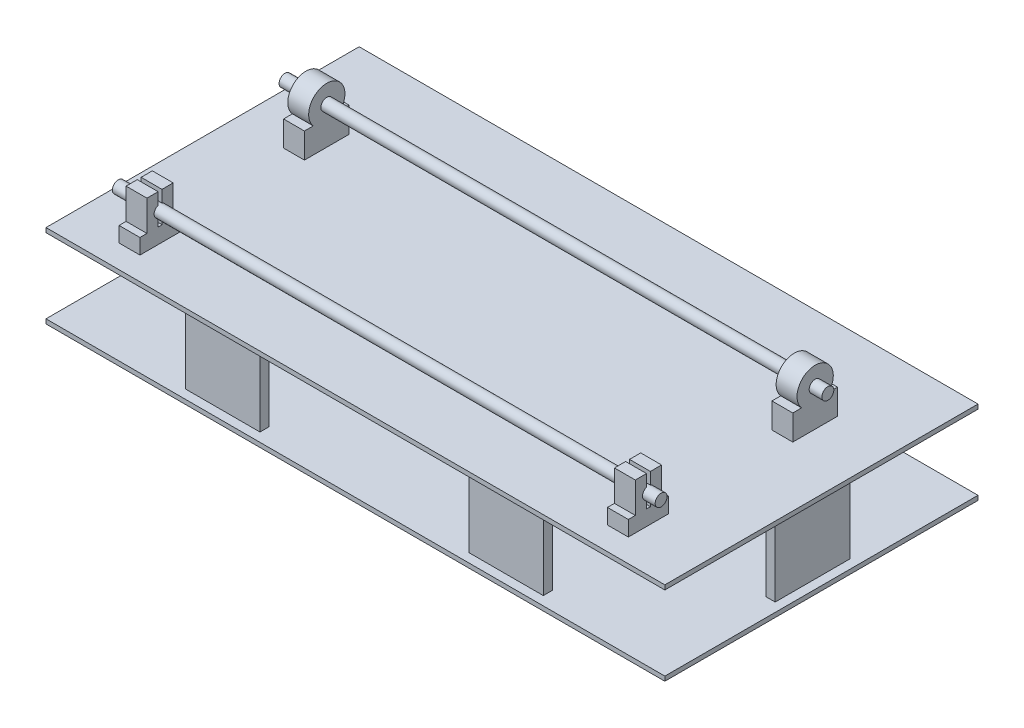
SolidWorks part; units mm, degrees
ref_plane "Front Plane" through (0, 0, 0) normal (0, 0, 1) x (1, 0, 0)
ref_plane "Top Plane" through (0, 0, 0) normal (0, 1, 0) x (1, 0, 0)
ref_plane "Right Plane" through (0, 0, 0) normal (1, 0, 0) x (0, 0, -1)
sketch "Sketch2" plane through (0, 0, 0) normal (0, 1, 0) x (1, 0, 0)
  line L1 (0, 0) -> (415, 0)
  line L2 (0, 0) -> (0, 210)
  line L3 (0, 210) -> (415, 210)
  line L4 (415, 0) -> (415, 210)
  dimension "D1" = 415
  dimension "D2" = 210
extrude "Boss-Extrude1" add sketch "Sketch2" along normal blind 3
ref_plane "Plane1" through (0, 53, 0) normal (0, 1, 0) x (1, 0, 0)
sketch "Sketch3" plane through (0, 53, 0) normal (0, 1, 0) x (1, 0, 0)
  line L8 (0, 210) -> (0, 0)
  line L9 (0, 0) -> (415, 0)
  line L10 (415, 0) -> (415, 210)
  line L11 (415, 210) -> (0, 210)
  line L12 (0, 210) -> (0, 0)
  line L13 (0, 0) -> (415, 0)
  line L14 (415, 0) -> (415, 210)
  line L15 (415, 210) -> (0, 210)
  dimension "D1" = 0
extrude "Boss-Extrude2" add sketch "Sketch3" along normal blind 3 separate body
sketch "Sketch4" plane through (0, 3, 0) normal (0, 1, 0) x (1, 0, 0)
  line L0 (0, 210) -> (0, 0) construction
  line L1 (6, 130) -> (12, 130)
  line L2 (6, 130) -> (6, 80)
  line L3 (6, 80) -> (12, 80)
  line L4 (12, 130) -> (12, 80)
  line L5 (87.5, 12) -> (137.5, 12)
  line L6 (87.5, 12) -> (87.5, 6)
  line L7 (87.5, 6) -> (137.5, 6)
  line L8 (137.5, 12) -> (137.5, 6)
  line L9 (277.5, 12) -> (327.5, 12)
  line L10 (277.5, 12) -> (277.5, 6)
  line L11 (277.5, 6) -> (327.5, 6)
  line L12 (327.5, 12) -> (327.5, 6)
  line L13 (409, 80) -> (403, 80)
  line L14 (409, 80) -> (409, 130)
  line L15 (409, 130) -> (403, 130)
  line L16 (403, 80) -> (403, 130)
  line L17 (327.5, 198) -> (277.5, 198)
  line L18 (327.5, 198) -> (327.5, 204)
  line L19 (327.5, 204) -> (277.5, 204)
  line L20 (277.5, 198) -> (277.5, 204)
  line L21 (137.5, 198) -> (87.5, 198)
  line L22 (137.5, 198) -> (137.5, 204)
  line L23 (137.5, 204) -> (87.5, 204)
  line L24 (87.5, 198) -> (87.5, 204)
  line L25 (0, 0) -> (415, 0) construction
  line L26 (415, 0) -> (415, 210) construction
  line L27 (415, 210) -> (0, 210) construction
  line L28 (0, 105) -> (415, 105) construction
  line L29 (207.5, 210) -> (207.5, 0) construction
  dimension "D1" = 50
  dimension "D2" = 6
  dimension "D3" = 50
  dimension "D4" = 6
  dimension "D5" = 50
  dimension "D6" = 6
  dimension "D7" = 50
  dimension "D8" = 6
  dimension "D9" = 50
  dimension "D10" = 6
  dimension "D11" = 50
  dimension "D12" = 6
  dimension "D13" = 6
  dimension "D14" = 6
  dimension "D15" = 6
  dimension "D16" = 6
  dimension "D17" = 6
  dimension "D18" = 6
  dimension "D19" = 70
  dimension "D20" = 70
  dimension "D21" = 70
  dimension "D22" = 70
  dimension "D23" = 25
  dimension "D24" = 25
extrude "Boss-Extrude3" add sketch "Sketch4" along normal up to surface (50 mm away) up to plane "Plane1"
ref_plane "Plane2" through (33.5, 0, 0) normal (-1, 0, 0) x (0, 0, 1)
sketch "Sketch5" plane through (33.5, 0, 0) normal (-1, 0, 0) x (0, 0, 1)
  line L0 (0, 56) -> (-210, 56) construction
  line L1 (-140.8, 81) -> (-140.8, 48.6428) construction
  line L2 (0, 56) -> (0, 53) construction
  line L3 (-29, 87.7809) -> (-29, 60.1422) construction
  line L4 (-20.2, 86.7193) -> (-27.7, 86.7193)
  line L5 (-20.2, 86.7193) -> (-20.2, 56)
  line L6 (-20.2, 56) -> (-27.7, 56)
  line L7 (-27.7, 86.7193) -> (-27.7, 56)
  line L9 (-30.3, 86.7808) -> (-37.8, 86.7808)
  line L10 (-30.3, 86.7808) -> (-30.3, 56)
  line L11 (-30.3, 56) -> (-37.8, 56)
  line L12 (-37.8, 86.7808) -> (-37.8, 56)
  line L13 (-42.5, 66.2205) -> (-15.5, 66.2205)
  line L14 (-42.5, 66.2205) -> (-42.5, 56)
  line L15 (-42.5, 56) -> (-15.5, 56)
  line L16 (-15.5, 66.2205) -> (-15.5, 56)
  line L17 (-155.8, 72.9129) -> (-125.8, 72.9129)
  line L18 (-155.8, 72.9129) -> (-155.8, 56)
  line L19 (-155.8, 56) -> (-125.8, 56)
  line L20 (-125.8, 72.9129) -> (-125.8, 56)
  circle A0 centre (-29, 75) radius 4
  circle A1 centre (-140.8, 81) radius 4
  circle A2 centre (-140.8, 81) radius 12.1653
  dimension "D1" = 8
  dimension "D2" = 8
  dimension "D3" = 19
  dimension "D4" = 29
  dimension "D5" = 69.2
  dimension "D6" = 25
  dimension "D7" = 1.3
  dimension "D8" = 1.3
  dimension "D9" = 7.5
  dimension "D10" = 7.5
  dimension "D11" = 27
  dimension "D12" = 13.5
  dimension "D13" = 15
  dimension "D14" = 15
extrude "Boss-Extrude4" add sketch "Sketch5" against normal blind 14 contours A0 L10 L9 L12 L13 | A0 L7 L13 L5 L4 | L13 L7 L6 L5 | L14 L15 L12 L13 | L13 L12 L11 L10 | L10 L15 L7 L13 | L16 L13 L5 L15 | A2 | L18 L17 L20 L19 region at (33.5, 76.6279, -23.6673) region at (33.5, 61.1102, -17.85) region at (33.5, 61.1102, -23.95) region at (33.5, 61.1102, -29) region at (33.5, 76.6614, -34.3318) region at (33.5, 61.1102, -34.05) region at (33.5, 61.1102, -40.15)
extrude "Boss-Extrude5" add sketch "Sketch5<3>" against normal blind 350 contours A1 | L10 A0 | L7 A0 L10 | L7 A0 region at (33.5, 75, -26.581) region at (33.5, 75, -29) region at (33.5, 75, -31.419) region at (33.5, 81, -140.8)
sketch "Sketch5<3>" plane through (33.5, 0, 0) normal (-1, 0, 0) x (0, 0, 1) same geometry as "Sketch5"
ref_plane "Plane3" through (361, 0, 0) normal (1, 0, 0) x (0, 0, -1)
sketch "Sketch8" plane through (361, 0, 0) normal (1, 0, 0) x (0, 0, -1)
  line L1 (140.8, 81) -> (140.8, 48.6428) construction
  line L3 (29, 87.7809) -> (29, 60.1422) construction
  line L4 (37.8, 86.7193) -> (30.3, 86.7193)
  line L5 (37.8, 86.7193) -> (37.8, 56)
  line L6 (37.8, 56) -> (30.3, 56)
  line L7 (30.3, 86.7193) -> (30.3, 56)
  line L9 (27.7, 86.7808) -> (20.2, 86.7808)
  line L10 (27.7, 86.7808) -> (27.7, 56)
  line L11 (27.7, 56) -> (20.2, 56)
  line L12 (20.2, 86.7808) -> (20.2, 56)
  line L13 (15.5, 66.2205) -> (42.5, 66.2205)
  line L14 (15.5, 66.2205) -> (15.5, 56)
  line L15 (15.5, 56) -> (42.5, 56)
  line L16 (42.5, 66.2205) -> (42.5, 56)
  line L17 (125.8, 72.9129) -> (155.8, 72.9129)
  line L18 (125.8, 72.9129) -> (125.8, 56)
  line L19 (125.8, 56) -> (155.8, 56)
  line L20 (155.8, 72.9129) -> (155.8, 56)
  circle A0 centre (29, 75) radius 4
  circle A1 centre (140.8, 81) radius 4
  circle A2 centre (140.8, 81) radius 12.1653
  dimension "D1" = 8
  dimension "D2" = 8
  dimension "D7" = 1.3
  dimension "D8" = 1.3
  dimension "D9" = 7.5
  dimension "D10" = 7.5
  dimension "D11" = 27
  dimension "D12" = 13.5
  dimension "D13" = 15
  dimension "D14" = 15
extrude "Boss-Extrude6" add sketch "Sketch8" along normal blind 14 contours A0 L10 L9 L12 L13 | A0 L7 L13 L5 L4 | L16 L13 L5 L15 | L13 L7 L6 L5 | L10 L15 L7 L13 | L14 L15 L12 L13 | A2 L17 L18 L19 L20 | L17 A2 | L17 A2 A1 | L10 L11 L12 L9 region at (361, 76.6279, -34.3327) region at (361, 61.1102, -40.15) region at (361, 61.1102, -34.05) region at (361, 61.1102, -29) region at (361, 76.6614, -23.6682) region at (361, 61.1102, -17.85) region at (361, 63.6908, -140.8) region at (361, 92.0742, -136.5862) region at (361, 71.2556, -140.8)
extrude "Boss-Extrude7" add sketch "Sketch5<4>" along normal blind 14 contours A1 | L7 A0 | L7 A0 L10 | L10 A0 region at (33.5, 75, -26.581) region at (33.5, 75, -29) region at (33.5, 75, -31.419) region at (33.5, 81, -140.8)
sketch "Sketch5<4>" plane through (33.5, 0, 0) normal (-1, 0, 0) x (0, 0, 1) same geometry as "Sketch5"
